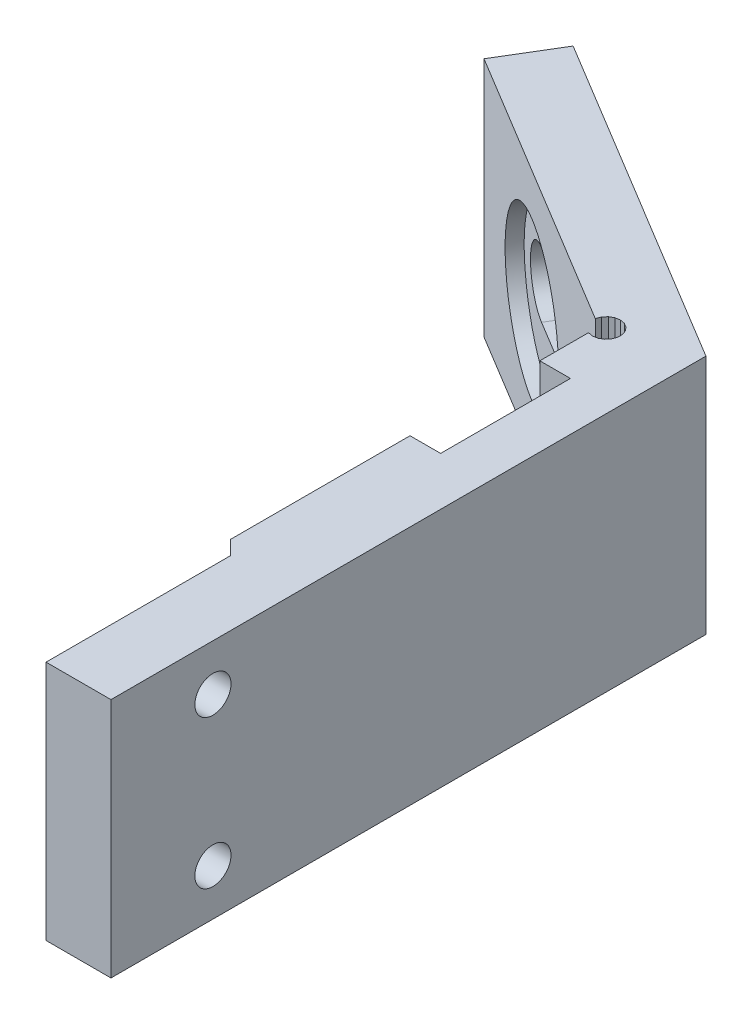
SolidWorks part; units mm, degrees
ref_plane "Front Plane" through (0, 0, 0) normal (0, 0, 1) x (1, 0, 0)
ref_plane "Top Plane" through (0, 0, 0) normal (0, 1, 0) x (1, 0, 0)
ref_plane "Right Plane" through (0, 0, 0) normal (1, 0, 0) x (0, 0, -1)
ref_plane "PY -20.700" through (0, -20.7, 0) normal (0, 1, 0) x (1, 0, 0)
sketch "leg and pad sketch" plane through (0, -20.7, 0) normal (0, 1, 0) x (1, 0, 0)
  line L0 (-0.5513, 30.3327) -> (-0.3673, 30.8194)
  line L1 (-0.3673, 30.8194) -> (-0.028, 31.2139)
  line L2 (-0.028, 31.2139) -> (0.4256, 31.4688)
  line L3 (0.4256, 31.4688) -> (0.939, 31.5534)
  line L4 (0.939, 31.5534) -> (1.4504, 31.4576)
  line L5 (1.4504, 31.4576) -> (1.8983, 31.1928)
  line L6 (1.8983, 31.1928) -> (2.2288, 30.7909)
  line L7 (2.2288, 30.7909) -> (2.4021, 30.3003)
  line L8 (2.4021, 30.3003) -> (2.3973, 29.78)
  line L9 (2.3973, 29.78) -> (2.2152, 29.2926)
  line L10 (2.2152, 29.2926) -> (1.8775, 28.8968)
  line L11 (1.8775, 28.8968) -> (1.4248, 28.6402)
  line L12 (1.4248, 28.6402) -> (0.9118, 28.5536)
  line L13 (0.9118, 28.5536) -> (0.4, 28.6475)
  line L14 (0.4, 28.6475) -> (0.4, -9.98)
  line L15 (0.4, -9.98) -> (1.92, -11.5)
  line L16 (1.92, -11.5) -> (1.92, -31.37)
  line L17 (1.92, -31.37) -> (8.92, -31.37)
  line L18 (8.92, -31.37) -> (8.92, 32.7926)
  line L19 (8.92, 32.7926) -> (-27.2048, 54.5947)
  line L20 (-27.2048, 54.5947) -> (-30.8218, 48.6015)
  line L21 (-30.8218, 48.6015) -> (-0.5513, 30.3327)
extrude "leg and pad" add sketch "leg and pad sketch" along normal mid plane 26
ref_plane "PX 1.350" through (1.35, 0, 0) normal (1, 0, 0) x (0, 0, -1)
sketch "screw head relief sketch" plane through (1.35, 0, 0) normal (1, 0, 0) x (0, 0, -1)
  line L0 (23.4, -12.7) -> (23.4, -6.7)
  line L1 (23.4, -6.7) -> (9.4, -6.7)
  line L2 (9.4, -6.7) -> (9.4, -12.7)
  line L3 (9.4, -12.7) -> (23.4, -12.7)
extrude "screw head relief" cut sketch "screw head relief sketch" against normal mid plane 4.7
sketch "insert flange relief sketch" plane through (0, -20.7, 0) normal (0, 1, 0) x (1, 0, 0)
  line L0 (-18.3249, 39.8914) -> (-17.0331, 42.0318)
  line L1 (-17.0331, 42.0318) -> (-9.7557, 37.6398)
  line L2 (-9.7557, 37.6398) -> (-11.0475, 35.4994)
  line L3 (-11.0475, 35.4994) -> (-18.3249, 39.8914)
revolve "insert flange relief" cut sketch "insert flange relief sketch" angle 360 about L0
sketch "M6 slot end 1 sketch" plane through (0, -20.7, 0) normal (0, 1, 0) x (1, 0, 0)
  line L0 (-20.8933, 41.4415) -> (-16.243, 49.147)
  line L1 (-16.243, 49.147) -> (-13.2464, 47.3385)
  line L2 (-13.2464, 47.3385) -> (-17.8968, 39.633)
  line L3 (-17.8968, 39.633) -> (-20.8933, 41.4415)
revolve "M6 slot end 1" cut sketch "M6 slot end 1 sketch" angle 360 about L0
sketch "M6 slot end 2 sketch" plane through (0, -20.7, 0) normal (0, 1, 0) x (1, 0, 0)
  line L0 (-15.7564, 38.3413) -> (-11.106, 46.0467)
  line L1 (-11.106, 46.0467) -> (-8.1094, 44.2382)
  line L2 (-8.1094, 44.2382) -> (-12.7598, 36.5328)
  line L3 (-12.7598, 36.5328) -> (-15.7564, 38.3413)
revolve "M6 slot end 2" cut sketch "M6 slot end 2 sketch" angle 360 about L0
sketch "M6 slot middle sketch" plane through (0, -20.7, 0) normal (0, 1, 0) x (1, 0, 0)
  line L0 (-15.7564, 38.3413) -> (-20.8933, 41.4415)
  line L1 (-20.8933, 41.4415) -> (-16.243, 49.147)
  line L2 (-16.243, 49.147) -> (-11.106, 46.0467)
  line L3 (-11.106, 46.0467) -> (-15.7564, 38.3413)
extrude "M6 slot middle" cut sketch "M6 slot middle sketch" against normal mid plane 7
ref_plane "PX 5.420" through (5.42, 0, 0) normal (1, 0, 0) x (0, 0, -1)
sketch "screw holes sketch" plane through (5.42, 0, 0) normal (1, 0, 0) x (0, 0, -1)
  circle A0 centre (-20.375, -28.7) radius 1.95
  circle A1 centre (-20.375, -12.7) radius 1.95
extrude "screw holes" cut sketch "screw holes sketch" against normal mid plane 9
equation "\"diffL\" = 608.8mm"
equation "\"diffW\" = 329.4mm"
equation "\"diffT\" = 2.9mm"
equation "\"chanSlotW\" = 12.9mm"
equation "\"chanSlotDepth\" = 11.13mm"
equation "\"chanFloor\" = 1.57mm"
equation "\"chanLeg\" = 12.7mm"
equation "\"lightL\" = 605mm"
equation "\"lightW\" = 331mm"
equation "\"lightH\" = 92mm"
equation "\"lightSideFlat\" = 30mm"
equation "\"lightSlopeLen\" = 33.1mm"
equation "\"lightWingDepth\" = 47.9mm"
equation "\"lightWingFlat\" = 90.2mm"
equation "\"lightChanW\" = 99.6mm"
equation "\"lightChanStand\" = 44.1mm"
equation "\"insFlangeD\" = 12.3mm"
equation "\"insFromEnd\" = 20.7mm"
equation "\"insUpSlope\" = 20.8mm"
equation "\"gaugeH\" = 10mm"
equation "\"gaugeStepLen\" = 14mm"
equation "\"gaugeStepW0\" = 13.1mm"
equation "\"gaugeStepDW\" = 0.2mm"
equation "\"gaugeSteps\" = 5mm"
equation "\"gaugeHandleLen\" = 30mm"
equation "\"gaugeHandleW\" = 24mm"
equation "\"gaugeSlot0\" = 3mm"
equation "\"gaugeSlotD\" = 0.1mm"
equation "\"gaugeSlotDepth\" = 8mm"
equation "\"gap\" = 25.4mm"
equation "\"edgeL\" = 1mm"
equation "\"edgeW\" = 0.75mm"
equation "\"proud\" = 1.5mm"
equation "\"seatClr\" = 0.15mm"
equation "\"tongueClrZ\" = 0.1mm"
equation "\"tongueClrX\" = 0.25mm"
equation "\"tongueLen\" = 30mm"
equation "\"armSide\" = 45mm"
equation "\"armEnd\" = 20mm"
equation "\"cornerCham\" = 3mm"
equation "\"brkW\" = 26mm"
equation "\"brkT\" = 7mm"
equation "\"brkSeatClr\" = 0.2mm"
equation "\"brkScrewSpan\" = 16mm"
equation "\"pilotD\" = 2.7mm"
equation "\"pilotDepth\" = 10mm"
equation "\"screwClrD\" = 3.9mm"
equation "\"jogBelow\" = 4mm"
equation "\"padT\" = 7mm"
equation "\"padLen\" = 31mm"
equation "\"m6Clr\" = 7mm"
equation "\"m6Slot\" = 3mm"
equation "\"flangeRelD\" = 17mm"
equation "\"flangeRelDepth\" = 1.5mm"
equation "\"relLen\" = 7mm"
equation "\"relDepth\" = 4mm"
equation "\"relLand\" = 2mm"
equation "\"knockN\" = 100mm"
equation "\"petgcfE\" = 3000mm"
equation "\"mockExtent\" = 110mm"
equation "\"relZnear\" = 9.4mm"
equation "\"relZfar\" = 23.4mm"
equation "\"headD\" = 8mm"
equation "\"headH\" = 2.5mm"
equation "\"headFromEnd\" = 6.8mm"
equation "\"headBack\" = 16.4mm"
equation "\"sideClr\" = 0.4mm"
equation "\"cornerRelR\" = 1.5mm"
equation "\"cornerRelBack\" = 0.6mm"
